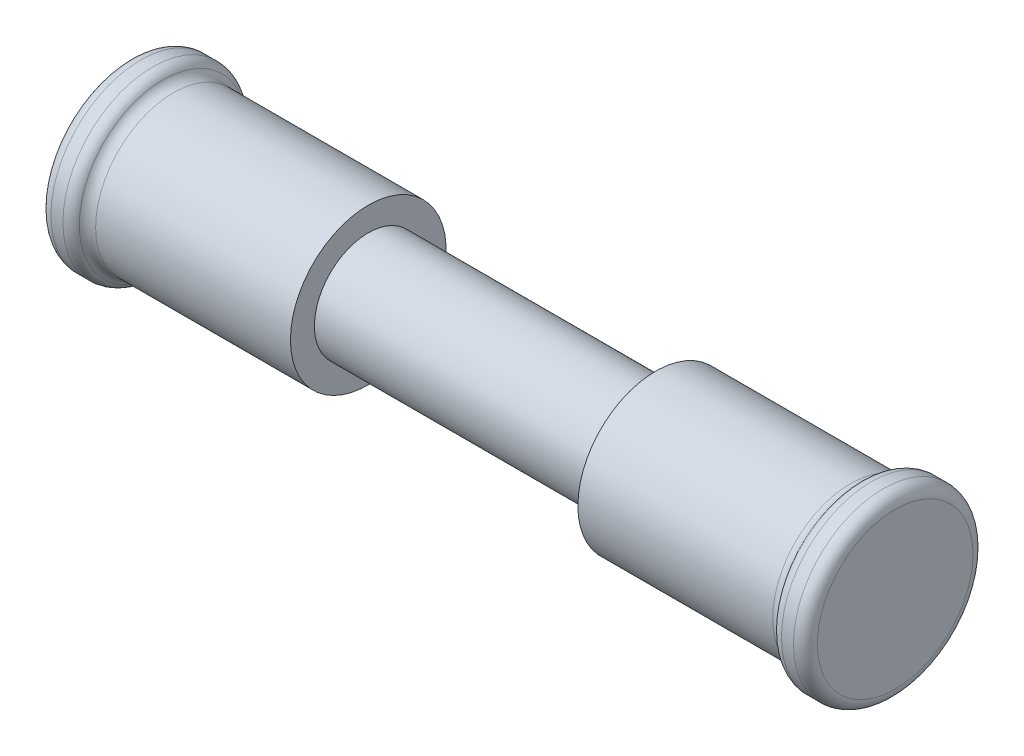
SolidWorks part; units mm, degrees
ref_plane "Front Plane" through (0, 0, 0) normal (0, 0, 1) x (1, 0, 0)
ref_plane "Top Plane" through (0, 0, 0) normal (0, 1, 0) x (1, 0, 0)
ref_plane "Right Plane" through (0, 0, 0) normal (1, 0, 0) x (0, 0, -1)
sketch "Sketch1" plane through (0, 0, 0) normal (1, 0, 0) x (0, 0, -1)
  circle A0 centre (0, 0) radius 2.25
  dimension "D1" = 4.5
extrude "Boss-Extrude1" add sketch "Sketch1" along normal mid plane 12
sketch "Sketch2" plane through (-6, 0, 0) normal (-1, 0, 0) x (0, 0, 1)
  circle A2 centre (0, 0) radius 3.25
  circle A3 centre (0, 0) radius 3.25
  dimension "D1" = 1
extrude "Boss-Extrude2" add sketch "Sketch2" along normal blind 10
sketch "Sketch3" plane through (-16, 0, 0) normal (-1, 0, 0) x (0, 0, 1)
  circle A2 centre (0, 0) radius 3.75
  circle A3 centre (0, 0) radius 3.75
  dimension "D1" = 0.5
extrude "Boss-Extrude3" add sketch "Sketch3" against normal blind 1.5
fillet "Fillet1" radius 0.5 2 edges at (-14.5, 0, 3.75) (-16, 0, 3.75)
fillet "Fillet2" radius 0.5 1 edges at (-14.5, 0, 3.25)
mirror "Mirror1" about plane through (0, 0, 0) normal (1, 0, 0) of "Boss-Extrude3", "Boss-Extrude2", "Fillet1", "Fillet2"
